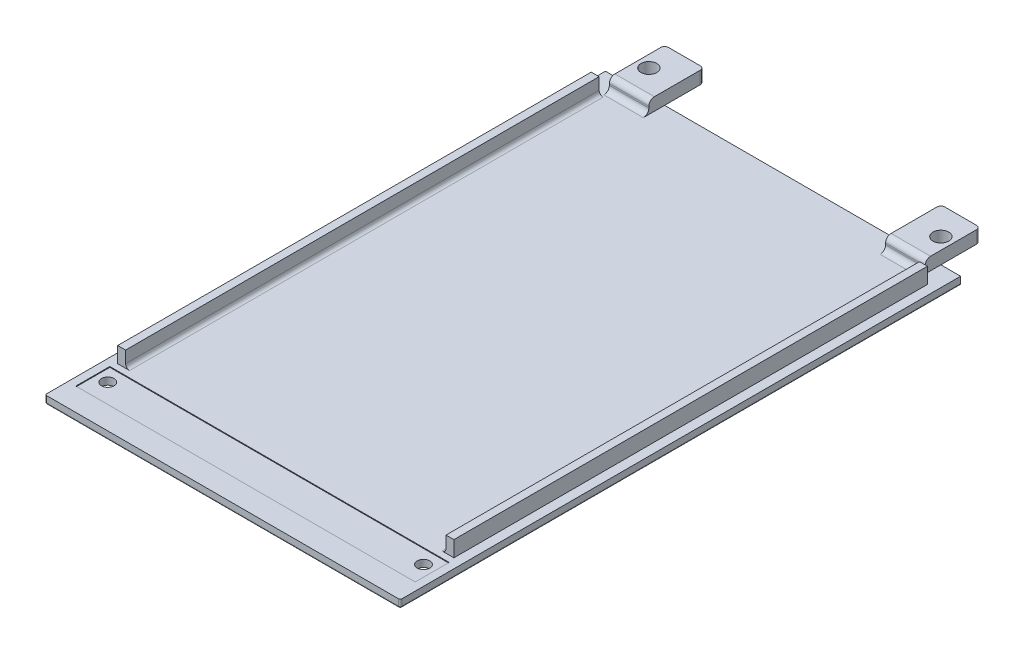
SolidWorks part; units mm, degrees
ref_plane "Front Plane" through (0, 0, 0) normal (0, 0, 1) x (1, 0, 0)
ref_plane "Top Plane" through (0, 0, 0) normal (0, 1, 0) x (1, 0, 0)
ref_plane "Right Plane" through (0, 0, 0) normal (1, 0, 0) x (0, 0, -1)
sketch "Sketch1" plane through (0, 0, 0) normal (0, 0, 1) x (1, 0, 0)
  line L1 (0, 0) -> (90, 0)
  line L2 (0, 0) -> (0, 2)
  line L3 (0, 2) -> (90, 2)
  line L4 (90, 0) -> (90, 2)
  dimension "D1" = 2
  dimension "D2" = 90
extrude "Boss-Extrude1" add sketch "Sketch1" along normal blind 142
fillet "Fillet1" radius 0.4 5 edges at (45, 0, 142) (0, 0, 71) (90, 0, 71) (0, 1, 142) (90, 1, 142)
sketch "Sketch2" plane through (0, 2, 0) normal (0, 1, 0) x (1, 0, 0)
  line L0 (45, 10.7962) -> (45, -52.5659) construction
  line L1 (5, -4) -> (15, -4)
  line L2 (5, -4) -> (5, 10)
  line L3 (5, 10) -> (15, 10)
  line L4 (15, -4) -> (15, 10)
  line L5 (90, -141.6) -> (90, 0) construction
  line L6 (0, -141.6) -> (0, 0) construction
  line L7 (90, 0) -> (0, 0) construction
  line L8 (85, 10) -> (75, 10)
  line L9 (75, -4) -> (75, 10)
  line L10 (85, -4) -> (75, -4)
  line L11 (85, -4) -> (85, 10)
  dimension "D1" = 5
  dimension "D2" = 4
  dimension "D3" = 10
  dimension "D4" = 14
extrude "Boss-Extrude2" add sketch "Sketch2" along normal blind 3.2
sketch "Sketch3" plane through (0, 2, 0) normal (0, -1, 0) x (1, 0, 0)
  line L0 (0, 0) -> (0, 141.6) construction
  line L1 (0.4, 0) -> (89.6, 0) construction
  line L2 (45, -16.5426) -> (45, 18.7189) construction
  line L3 (90, 141.6) -> (90, 0) construction
  line L4 (0, 141.6) -> (0, 0) construction
  circle A0 centre (8, -3) radius 2
  circle A1 centre (82, -3) radius 2
  dimension "D2" = 4
  dimension "D3" = 3
  dimension "D1" = 8
extrude "Cut-Extrude10" cut sketch "Sketch3" against normal blind 3.2
sketch "Sketch4" plane through (0, 2, 0) normal (0, 1, 0) x (1, 0, 0)
  line L0 (45, -201.0182) -> (45, -82.9818) construction
  line L2 (89.6, -142) -> (0.4, -142) construction
  line L3 (0, -141.6) -> (0, 0) construction
  circle A0 centre (5, -131.1) radius 1.6
  circle A1 centre (85, -131.1) radius 1.6
  point P3 (45, -142)
  dimension "D2" = 10.9
  dimension "D3" = 3.2
  dimension "D1" = 5
extrude "Cut-Extrude11" cut sketch "Sketch4" against normal through all
sketch "Sketch5" plane through (0, 2, 0) normal (0, 1, 0) x (1, 0, 0)
  line L0 (2.4, -6) -> (2.4, -126)
  line L1 (2.4, -126) -> (4.4, -126)
  line L2 (4.4, -126) -> (4.4, -6)
  line L3 (4.4, -6) -> (2.4, -6)
  line L4 (45, 0) -> (45, -142) construction
  line L5 (75, 0) -> (15, 0) construction
  line L6 (89.6, -142) -> (0.4, -142) construction
  line L7 (87.6, -126) -> (85.6, -126)
  line L8 (87.6, -6) -> (87.6, -126)
  line L9 (85.6, -6) -> (87.6, -6)
  line L10 (85.6, -126) -> (85.6, -6)
  line L11 (5, 0) -> (0, 0) construction
  line L12 (0, -141.6) -> (0, 0) construction
  dimension "D1" = 6
  dimension "D2" = 2.4
  dimension "D3" = 2
  dimension "D4" = 16
extrude "Boss-Extrude3" add sketch "Sketch5" along normal blind 4
sketch "Sketch6" plane through (0, 2, 0) normal (0, 1, 0) x (1, 0, 0)
  line L0 (45, -142) -> (45, -96.1356) construction
  line L1 (2, -136.2) -> (88, -136.2)
  line L2 (2, -136.2) -> (2, -127.6)
  line L3 (2, -127.6) -> (88, -127.6)
  line L4 (88, -136.2) -> (88, -127.6)
  line L5 (89.6, -142) -> (0.4, -142) construction
  line L6 (0, -141.6) -> (0, 0) construction
  dimension "D1" = 2
  dimension "D2" = 5.8
  dimension "D3" = 8.6
extrude "Cut-Extrude12" cut sketch "Sketch6" against normal blind 0.2
fillet "Fillet2" radius 1.4 4 edges at (10, 5.2, 4) (10, 2, 4) (80, 5.2, 4) (80, 2, 4)
fillet "Fillet4" radius 1 4 edges at (75, 3.6, -10) (85, 3.6, -10) (15, 3.6, -10) (5, 3.6, -10)
fillet "Fillet5" radius 1 2 edges at (85.6, 2, 66) (4.4, 2, 66)
